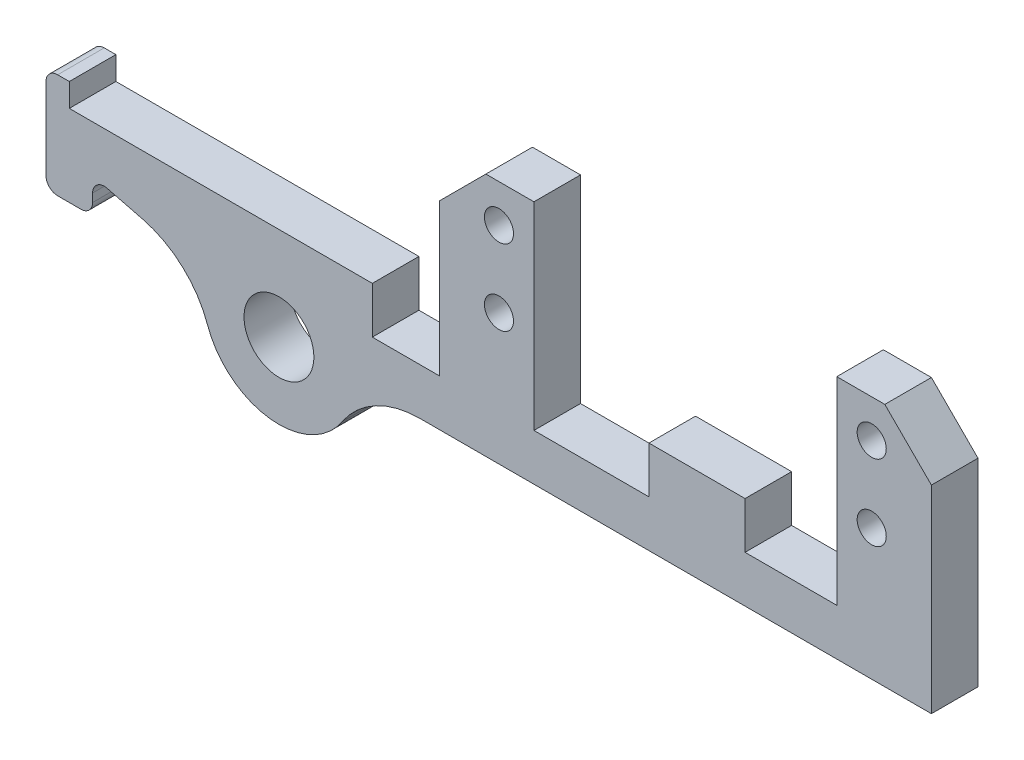
SolidWorks part; units mm, degrees
ref_plane "Front Plane" through (0, 0, 0) normal (0, 0, 1) x (1, 0, 0)
ref_plane "Top Plane" through (0, 0, 0) normal (0, 1, 0) x (1, 0, 0)
ref_plane "Right Plane" through (0, 0, 0) normal (1, 0, 0) x (0, 0, -1)
sketch "Sketch1" plane through (0, 136.6763, 0) normal (0, 1, 0) x (1, 0, 0)
  line L0 (-27.651, -32.4827) -> (-27.651, -60.4545) construction
  line L1 (-103.851, -54.1033) -> (-90.951, -54.1033)
  line L2 (-103.851, -54.1033) -> (-103.851, -60.4533)
  line L3 (-103.851, -60.4533) -> (-90.951, -60.4533)
  line L4 (-90.951, -54.1033) -> (-90.951, -60.4533)
  line L5 (-68.926, -54.1033) -> (-81.826, -54.1033)
  line L6 (-68.926, -54.1033) -> (-68.926, -60.4533)
  line L7 (-68.926, -60.4533) -> (-81.826, -60.4533)
  line L8 (-81.826, -54.1033) -> (-81.826, -60.4533)
  line L9 (-53.251, -54.1033) -> (-40.151, -54.1033)
  line L10 (-53.251, -54.1033) -> (-53.251, -60.4533)
  line L11 (-53.251, -60.4533) -> (-40.151, -60.4533)
  line L12 (-40.151, -54.1033) -> (-40.151, -60.4533)
  line L13 (-27.651, -54.1033) -> (-14.751, -54.1033)
  line L14 (-27.651, -54.1033) -> (-27.651, -60.4533)
  line L15 (-27.651, -60.4533) -> (-14.751, -60.4533)
  line L16 (-14.751, -54.1033) -> (-14.751, -60.4533)
  dimension "D1" = 12.9
  dimension "D2" = 13.1
  dimension "D3" = 12.9
  dimension "D4" = 12.9
  dimension "D5" = 50.6
extrude "Boss-Extrude1" add sketch "Sketch1" against normal blind 6.35
sketch "Sketch2" plane through (0, 130.3263, 0) normal (0, -1, 0) x (-1, 0, 0)
  line L1 (103.851, -60.4533) -> (14.951, -60.4533)
  line L2 (103.851, -60.4533) -> (103.851, -54.1033)
  line L3 (103.851, -54.1033) -> (14.951, -54.1033)
  line L4 (14.951, -60.4533) -> (14.951, -54.1033)
  dimension "D1" = 6.35
  dimension "D2" = 88.9
extrude "Boss-Extrude2" add sketch "Sketch2" along normal blind 12.7
sketch "Sketch3" plane through (0, 136.6763, 0) normal (0, 1, 0) x (1, 0, 0)
  line L1 (-68.926, -54.1033) -> (-81.826, -54.1033)
  line L2 (-68.926, -54.1033) -> (-68.926, -60.4533)
  line L3 (-68.926, -60.4533) -> (-81.826, -60.4533)
  line L4 (-81.826, -54.1033) -> (-81.826, -60.4533)
  line L5 (-14.751, -54.1033) -> (-27.651, -54.1033)
  line L6 (-14.751, -54.1033) -> (-14.751, -60.4533)
  line L7 (-14.751, -60.4533) -> (-27.651, -60.4533)
  line L8 (-27.651, -54.1033) -> (-27.651, -60.4533)
extrude "Boss-Extrude3" add sketch "Sketch3" along normal up to surface (20.6375 mm away)
chamfer "Chamfer1" distance 6.35 angle 45 2 edges at (-14.751, 157.3138, 57.2783) (-81.826, 157.3138, 57.2783)
sketch "Sketch4" plane through (0, 0, 60.4533) normal (0, 0, 1) x (1, 0, 0)
  circle A0 centre (-73.6885, 152.1544) radius 1.9844
  circle A1 centre (-73.6885, 141.8357) radius 1.9844
  circle A2 centre (-22.8885, 141.8357) radius 1.9844
  circle A3 centre (-22.8885, 152.1544) radius 1.9844
extrude "Cut-Extrude1" cut sketch "Sketch4" against normal through all
sketch "Sketch12" plane through (-14.951, 0, 0) normal (1, 0, 0) x (0, 0, -1)
  line L1 (-60.4533, 117.6263) -> (-54.1033, 117.6263)
  line L2 (-60.4533, 117.6263) -> (-60.4533, 130.3263)
  line L3 (-60.4533, 130.3263) -> (-54.1033, 130.3263)
  line L4 (-54.1033, 117.6263) -> (-54.1033, 130.3263)
extrude "Boss-Extrude6" add sketch "Sketch12" along normal up to surface (0.2 mm away) up to face at (-14.751, 140.645, 57.2783)
sketch "Sketch13" plane through (0, 0, 60.4533) normal (0, 0, 1) x (1, 0, 0)
  line L0 (-14.751, 117.6263) -> (-14.751, 150.9638) construction
  line L1 (-103.851, 117.6263) -> (-14.751, 117.6263)
  line L2 (-103.851, 117.6263) -> (-103.851, 123.9763)
  line L3 (-103.851, 123.9763) -> (-14.751, 123.9763)
  line L4 (-14.751, 117.6263) -> (-14.751, 123.9763)
  dimension "D1" = 6.35
extrude "Cut-Extrude2" cut sketch "Sketch13" against normal through all
sketch "Sketch14" plane through (0, 0, 60.4533) normal (0, 0, 1) x (1, 0, 0)
  line L1 (-132.251, 139.8513) -> (-135.426, 139.8513)
  line L2 (-132.251, 139.8513) -> (-132.251, 136.6763)
  line L4 (-135.426, 139.8513) -> (-135.426, 131.9138)
  line L5 (-103.851, 123.9763) -> (-135.426, 131.9138)
  line L6 (-103.851, 136.6763) -> (-132.251, 136.6763)
  line L7 (-103.851, 136.6763) -> (-103.851, 123.9763)
  dimension "D2" = 3.175
  dimension "D3" = 28.4
extrude "Boss-Extrude7" add sketch "Sketch14" against normal blind 6.35
sketch "Sketch19" plane through (0, 0, 60.4533) normal (0, 0, 1) x (1, 0, 0)
  circle A0 centre (-103.676, 123.9763) radius 10.3188
  circle A1 centre (-103.676, 123.9763) radius 4.7625
extrude "Boss-Extrude8" add sketch "Sketch19" against normal blind 6.35
sketch "Sketch20" plane through (0, 0, 60.4533) normal (0, 0, 1) x (1, 0, 0)
  circle A0 centre (-103.676, 123.9763) radius 4.7625
extrude "Cut-Extrude3" cut sketch "Sketch20" against normal through all both and the other way through all
fillet "Fillet2" radius 12.7 2 edges at (-113.6937, 126.4506, 57.2783) (-93.3572, 123.9763, 57.2783)
fillet "Fillet3" radius 1.5875 1 edges at (-135.426, 139.8513, 57.2783)
sketch "Sketch21" plane through (0, 0, 60.4533) normal (0, 0, 1) x (1, 0, 0)
  line L1 (-135.426, 131.9138) -> (-129.076, 131.9138)
  line L2 (-135.426, 131.9138) -> (-135.426, 125.5638)
  line L3 (-135.426, 125.5638) -> (-129.076, 125.5638)
  line L4 (-129.076, 131.9138) -> (-129.076, 125.5638)
  dimension "D1" = 6.35
  dimension "D2" = 6.35
extrude "Boss-Extrude9" add sketch "Sketch21" against normal up to surface (6.35 mm away) up to face at (-98.9135, 123.9763, 54.1033)
fillet "Fillet4" radius 1.5875 3 edges at (-129.076, 130.3175, 57.2783) (-135.426, 125.5638, 57.2783) (-129.076, 125.5638, 57.2783)
